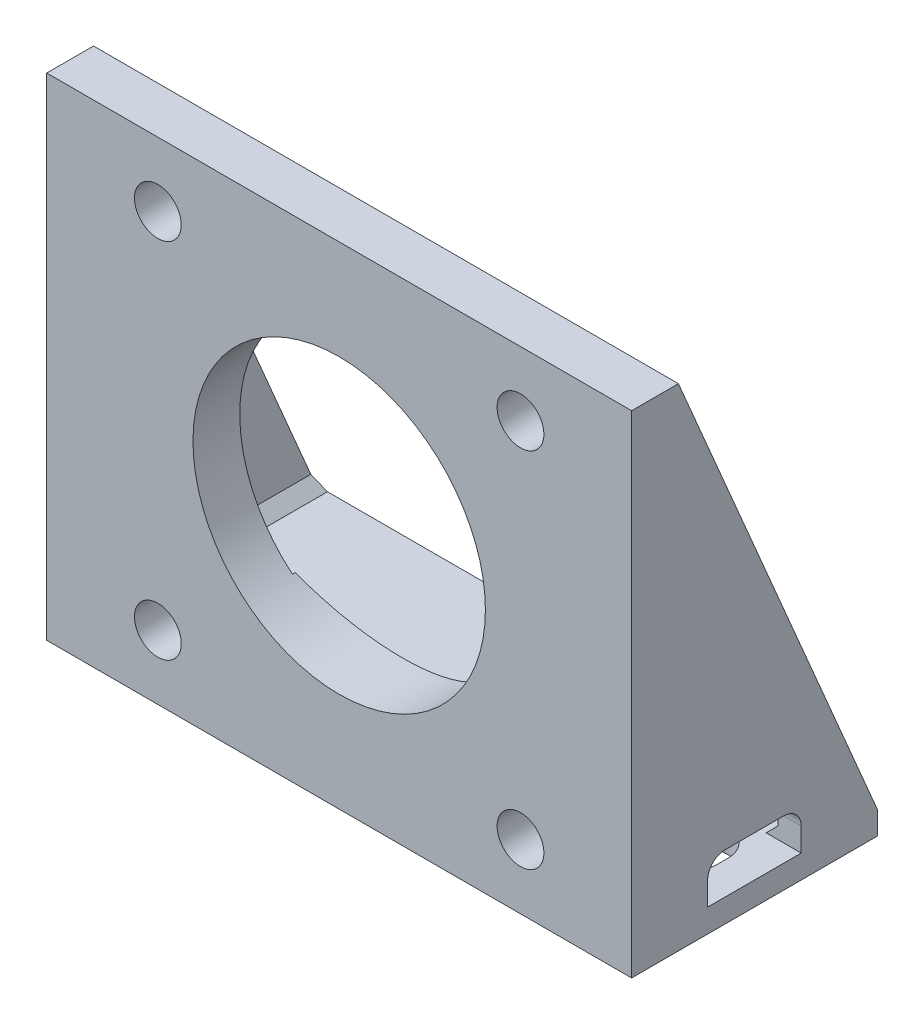
SolidWorks part; units mm, degrees
ref_plane "Front Plane" through (0, 0, 0) normal (0, 0, 1) x (1, 0, 0)
ref_plane "Top Plane" through (0, 0, 0) normal (0, 1, 0) x (1, 0, 0)
ref_plane "Right Plane" through (0, 0, 0) normal (1, 0, 0) x (0, 0, -1)
sketch "Sketch1" plane through (0, 0, 0) normal (0, 1, 0) x (1, 0, 0)
  line L0 (25, 21) -> (25, 0) construction
  line L1 (0, 0) -> (50, 0)
  line L2 (0, 0) -> (0, 21)
  line L3 (0, 21) -> (50, 21)
  line L4 (50, 0) -> (50, 21)
  line L5 (5, 11) -> (5, 10) construction
  line L6 (7.25, 11) -> (7.25, 10)
  line L7 (2.75, 11) -> (2.75, 10)
  line L8 (45, 11) -> (45, 10) construction
  line L9 (42.75, 11) -> (42.75, 10)
  line L10 (47.25, 11) -> (47.25, 10)
  line L11 (25, 16) -> (25, 15) construction
  line L12 (27.25, 16) -> (27.25, 15)
  line L13 (22.75, 16) -> (22.75, 15)
  arc A2 (7.25, 11) -> (2.75, 11) centre (5, 11) ccw
  arc A3 (2.75, 10) -> (7.25, 10) centre (5, 10) ccw
  arc A4 (42.75, 11) -> (47.25, 11) centre (45, 11) cw
  arc A5 (47.25, 10) -> (42.75, 10) centre (45, 10) cw
  arc A6 (27.25, 16) -> (22.75, 16) centre (25, 16) ccw
  arc A7 (22.75, 15) -> (27.25, 15) centre (25, 15) ccw
  point P7 (5, 10.5)
  point P16 (45, 10.5)
  point P23 (25, 15.5)
  dimension "D4" = 2.25
  dimension "D7" = 2.25
  dimension "D1" = 50
  dimension "D2" = 10
  dimension "D3" = 11
  dimension "D5" = 20
  dimension "D6" = 21
  dimension "D8" = 1
  dimension "D9" = 5
extrude "Boss-Extrude1" add sketch "Sketch1" along normal blind 2
sketch "Sketch2" plane through (0, 0, 0) normal (0, 0, 1) x (1, 0, 0)
  line L0 (50, 2) -> (50, 0) construction
  line L1 (0, 0) -> (50, 0)
  line L2 (0, 0) -> (0, 42)
  line L3 (0, 42) -> (50, 42)
  line L4 (50, 0) -> (50, 42)
  line L5 (25, 42) -> (25, 0) construction
  circle A0 centre (9.5, 36.5) radius 2
  circle A1 centre (9.5, 5.5) radius 2
  circle A2 centre (40.5, 5.5) radius 2
  circle A3 centre (40.5, 36.5) radius 2
  circle A4 centre (25, 21) radius 12.5
  dimension "D2" = 4
  dimension "D5" = 25
  dimension "D1" = 42
  dimension "D3" = 31
  dimension "D4" = 31
  dimension "D6" = 21
  dimension "D7" = 25
  dimension "D8" = 15.5
  dimension "D9" = 15.5
extrude "Boss-Extrude2" add sketch "Sketch2" against normal blind 4
sketch "Sketch3" plane through (50, 0, 0) normal (1, 0, 0) x (0, 0, -1)
  line L0 (21, 2) -> (4, 42)
  line L1 (4, 42) -> (4, 2)
  line L2 (4, 2) -> (6.5, 2)
  line L3 (10, 2) -> (10, 0) construction
  line L5 (6.5, 2) -> (6.5, 4)
  line L6 (8, 5.5) -> (13, 5.5)
  line L7 (14.5, 2) -> (14.5, 4)
  line L8 (11, 2) -> (11, 0) construction
  line L9 (14.5, 2) -> (21, 2)
  arc A0 (14.5, 4) -> (13, 5.5) centre (13, 4) ccw
  arc A1 (8, 5.5) -> (6.5, 4) centre (8, 4) ccw
  point P16 (14.5, 5.5)
  dimension "D4" = 1.5
  dimension "D1" = 3.5
  dimension "D2" = 3.5
  dimension "D3" = 3.5
extrude "Boss-Extrude3" add sketch "Sketch3" against normal up to surface (50 mm away)
sketch "Sketch4" plane through (0, 0, -21) normal (0, 0, -1) x (-1, 0, 0)
  line L0 (-50, 2) -> (0, 2) construction
  line L1 (-48, 2) -> (-2, 2)
  line L2 (-48, 2) -> (-48, 42)
  line L3 (-48, 42) -> (-2, 42)
  line L4 (-2, 2) -> (-2, 42)
  line L5 (-50, 42) -> (0, 42) construction
  line L6 (-50, 2) -> (-50, 42) construction
  line L7 (0, 42) -> (0, 2) construction
  dimension "D1" = 2
  dimension "D2" = 2
extrude "Cut-Extrude1" cut sketch "Sketch4" against normal up to vertex
ref_plane "Plane1" through (25, 0, 0) normal (-1, 0, 0) x (0, 0, 1)
sketch "Sketch5" plane through (25, 0, 0) normal (-1, 0, 0) x (0, 0, 1)
  line L0 (-4, 2) -> (-8, 2)
  line L1 (-7.75, 2) -> (-10, 2) construction
  line L2 (-8, 2) -> (-4, 12)
  line L3 (-4, 12) -> (-4, 2)
  line L4 (0, 0) -> (-21, 0) construction
  dimension "D1" = 4
  dimension "D2" = 12
extrude "Boss-Extrude4" add sketch "Sketch5" along normal blind 8 and the other way blind 8
sketch "Sketch6" plane through (0, 0, -4) normal (0, 0, 1) x (1, 0, 0)
  circle A0 centre (25, 21) radius 12.5
extrude "Cut-Extrude2" cut sketch "Sketch6" against normal through all
chamfer "Chamfer1" distance 1 angle 45 9 edges at (2, 2, -17.75) (2, 2, -5.25) (9.5, 2, -4) (17, 2, -6) (25, 2, -8) (33, 2, -6) (40.5, 2, -4) (48, 2, -5.25) (48, 2, -17.75)
chamfer "Chamfer2" distance 2 angle 45 2 edges at (48, 22.5, -4) (2, 22.5, -4)
